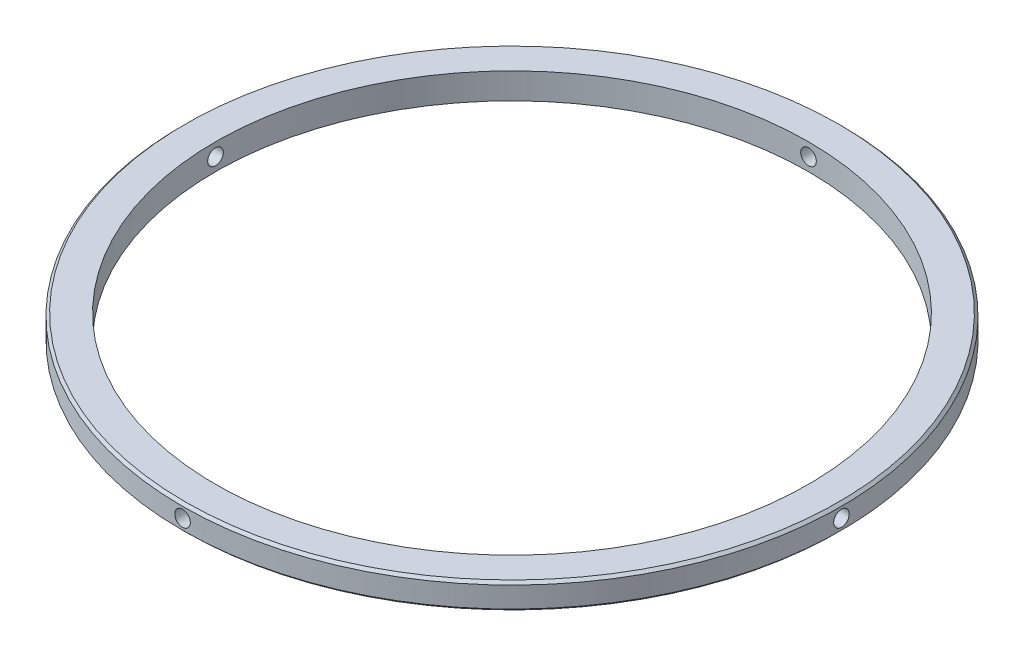
SolidWorks part; units mm, degrees
ref_plane "Front Plane" through (0, 0, 0) normal (0, 0, 1) x (1, 0, 0)
ref_plane "Top Plane" through (0, 0, 0) normal (0, 1, 0) x (1, 0, 0)
ref_plane "Right Plane" through (0, 0, 0) normal (1, 0, 0) x (0, 0, -1)
sketch "Outer Ring Main Sketch" plane through (0, 0, 0) normal (0, 1, 0) x (1, 0, 0)
  circle A0 centre (0, 0) radius 63.5
  dimension "D1" = 127
extrude "Outer Ring Main Body" add sketch "Outer Ring Main Sketch" along normal blind 5
sketch "Center Hole Sketch" plane through (0, 0, 0) normal (0, -1, 0) x (1, 0, 0)
  circle A0 centre (0, 0) radius 57.15
  dimension "D1" = 114.3
extrude "Center Hole" cut sketch "Center Hole Sketch" against normal through all
sketch "Pin Hole Sketch" plane through (0, 0, 0) normal (0, 0, 1) x (1, 0, 0)
  line L0 (-63.5, 5) -> (-63.5, 0) construction
  line L1 (63.5, 5) -> (-63.5, 5) construction
  line L2 (63.5, 0) -> (63.5, 5) construction
  line L3 (-63.5, 0) -> (63.5, 0) construction
  line L4 (-63.5, 5) -> (-63.5, 0) construction
  line L5 (63.5, 5) -> (-63.5, 5) construction
  line L6 (63.5, 0) -> (63.5, 5) construction
  line L7 (-63.5, 0) -> (63.5, 0) construction
  line L8 (0, 38.9259) -> (0, -26.8884) construction
  line L9 (78.5361, 2.5) -> (-89.9551, 2.5) construction
  circle A0 centre (0, 2.5) radius 1.5
  dimension "D6" = 3
  dimension "D1" = 63.5
  dimension "D2" = 127
  dimension "D3" = 5
  dimension "D4" = 2.5
  dimension "D5" = 0
extrude "Pin Hole" cut sketch "Pin Hole Sketch" against normal through all both and the other way through all
sketch "Pin Hole 2 Sketch" plane through (0, 0, 0) normal (1, 0, 0) x (0, 0, -1)
  line L0 (-63.5, 0) -> (63.5, 0) construction
  line L1 (63.5, 5) -> (-63.5, 5) construction
  line L2 (-63.5, 0) -> (63.5, 0) construction
  line L3 (63.5, 5) -> (-63.5, 5) construction
  line L4 (0, 32.931) -> (0, -21.2844) construction
  line L5 (69.0724, 2.5) -> (-67.7692, 2.5) construction
  circle A0 centre (0, 2.5) radius 1.5
  spline S0 degree 2 poles (63.5, 1) (63.4646, 2.5) (63.5, 4) knots 0 0 0 1 1 1 weights 0.062 0.0635 0.065 construction
  spline S1 degree 2 poles (-63.5, 4) (-63.4646, 2.5) (-63.5, 1) knots 0 0 0 1 1 1 weights 0.062 0.0635 0.065 construction
  spline S2 degree 2 poles (63.5, 1) (63.4646, 2.5) (63.5, 4) knots 0 0 0 1 1 1 weights 0.062 0.0635 0.065 construction
  spline S3 degree 2 poles (-63.5, 4) (-63.4646, 2.5) (-63.5, 1) knots 0 0 0 1 1 1 weights 0.062 0.0635 0.065 construction
  dimension "D6" = 3
  dimension "D2" = 127
  dimension "D5" = 0
  dimension "D1" = 5
  dimension "D3" = 2.5
  dimension "D4" = 63.5
extrude "Pin Hole 2" cut sketch "Pin Hole 2 Sketch" against normal through all both and the other way through all
chamfer "Outer Ring Chamfer" distance 0.5 angle 45 2 edges at (0, 5, 63.5) (0, 0, 63.5)
equation "\"D1@Pin Hole Sketch\" = \"D2@Pin Hole Sketch\" * 0.5"
equation "\"D4@Pin Hole Sketch\" = \"D3@Pin Hole Sketch\" * 0.5"
equation "\"D3@Pin Hole 2 Sketch\" = \"D1@Pin Hole 2 Sketch\" * 0.5"
equation "\"D4@Pin Hole 2 Sketch\" = \"D2@Pin Hole 2 Sketch\" * 0.5"
equation "\"D5@Pin Hole 2 Sketch\" = 0"
